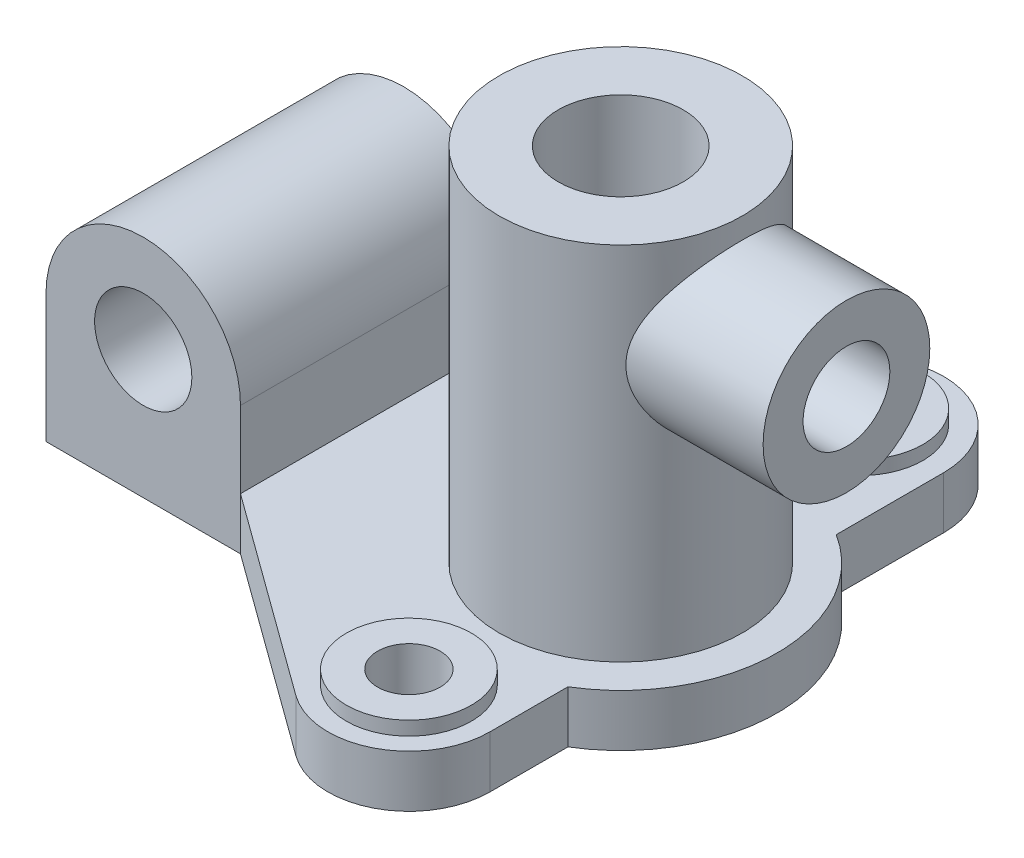
SolidWorks part; units mm, degrees
ref_plane "Front Plane" through (0, 0, 0) normal (0, 0, 1) x (1, 0, 0)
ref_plane "Top Plane" through (0, 0, 0) normal (0, 1, 0) x (1, 0, 0)
ref_plane "Right Plane" through (0, 0, 0) normal (1, 0, 0) x (0, 0, -1)
sketch "Sketch1" plane through (0, 0, 0) normal (0, 1, 0) x (1, 0, 0)
  line L0 (24, 38.0657) -> (24, 69)
  line L1 (-15.8749, 86.9997) -> (-72, 37.5)
  line L2 (-72, 37.5) -> (-72, -37.5)
  line L4 (-13.6963, -79.854) -> (-72, -37.5)
  line L5 (23.3037, -38.496) -> (23.3037, -61)
  line L7 (-72, 37.5) -> (-128, 37.5)
  line L8 (-72, 37.5) -> (-72, -37.5)
  line L9 (-72, -37.5) -> (-128, -37.5)
  line L10 (-128, 37.5) -> (-128, -37.5)
  circle A9 centre (0, 0) radius 18
  circle A10 centre (0, 0) radius 35
  arc A11 (23.3037, -38.496) -> (24, 38.0657) centre (0, 0) ccw
  arc A12 (24, 69) -> (-15.8749, 86.9997) centre (0, 69) ccw
  circle A13 centre (0, 69) radius 18
  circle A14 centre (0, 69) radius 9
  arc A15 (23.3037, -61) -> (-13.6963, -79.854) centre (0, -61) cw
  circle A16 centre (0, -61) radius 9
  circle A17 centre (0, -61) radius 18
  dimension "D1" = 48
  dimension "D2" = 36
  dimension "D3" = 18
  dimension "D4" = 90
  dimension "D5" = 70
  dimension "D6" = 36
  dimension "D7" = 56
  dimension "D8" = 75
  dimension "D9" = 128
  dimension "D10" = 130
extrude "Boss-Extrude1" add sketch "Sketch1" along normal blind 15 contours A15 L5 A11 L0 A12 L1 L2 L4 A13 A10 A17 region at (42.8739, 0, 0.3899)
extrude "Boss-Extrude2" add sketch "Sketch1<3>" along normal blind 119 contours A10 A9 region at (-34.0101, 0, 0)
sketch "Sketch1<3>" plane through (0, 0, 0) normal (0, 1, 0) x (1, 0, 0) same geometry as "Sketch1"
extrude "Boss-Extrude3" add sketch "Sketch1<4>" along normal blind 19 contours A17 A16 | A13 A14 region at (-17.4909, 0, -69) region at (-17.4909, 0, 61)
sketch "Sketch1<4>" plane through (0, 0, 0) normal (0, 1, 0) x (1, 0, 0) same geometry as "Sketch1"
extrude "Boss-Extrude4" add sketch "Sketch1<5>" along normal blind 65 contours L7 L10 L9 L2 region at (-100, 0, 0)
sketch "Sketch1<5>" plane through (0, 0, 0) normal (0, 1, 0) x (1, 0, 0) same geometry as "Sketch1"
sketch "Sketch2" plane through (0, 0, 0) normal (0, 0, 1) x (1, 0, 0)
  line L0 (-72, 65) -> (-128, 65) construction
  line L1 (-72, 65) -> (-72, 15) construction
  line L2 (-128, 65) -> (-128, 0) construction
  line L3 (-128, 37) -> (-114, 37)
  line L4 (-86, 37) -> (-72, 37)
  line L5 (-128, 37) -> (-128, 65)
  line L6 (-128, 65) -> (-72, 65)
  line L7 (-72, 65) -> (-72, 37)
  arc A0 (-72, 37) -> (-128, 37) centre (-100, 37) ccw
  circle A1 centre (-100, 37) radius 14
  dimension "D2" = 28
extrude "Cut-Extrude1" cut sketch "Sketch2" against normal blind 65 and the other way through all contours A0 L7 L6 | A0 L6 L5 | A1 region at (-121.7457, 58.7457, 0) region at (-100, 37, 0) region at (-78.2543, 58.7457, 0)
sketch "Sketch3" plane through (0, 0, 0) normal (1, 0, 0) x (0, 0, -1)
  circle A0 centre (0, 89) radius 24
  circle A1 centre (0, 89) radius 12.5
  dimension "D1" = 89
extrude "Boss-Extrude5" add sketch "Sketch3" along normal blind 65 contours A0 A1 region at (0, 89, 23.3212)
extrude "Cut-Extrude3" cut sketch "Sketch1<6>" along normal blind 263 contours A9 region at (0, 0, 0)
sketch "Sketch1<6>" plane through (0, 0, 0) normal (0, 1, 0) x (1, 0, 0) same geometry as "Sketch1"
extrude "Cut-Extrude4" cut sketch "Sketch3<3>" along normal blind 263 contours A1
sketch "Sketch3<3>" plane through (0, 0, 0) normal (1, 0, 0) x (0, 0, -1) same geometry as "Sketch3"
